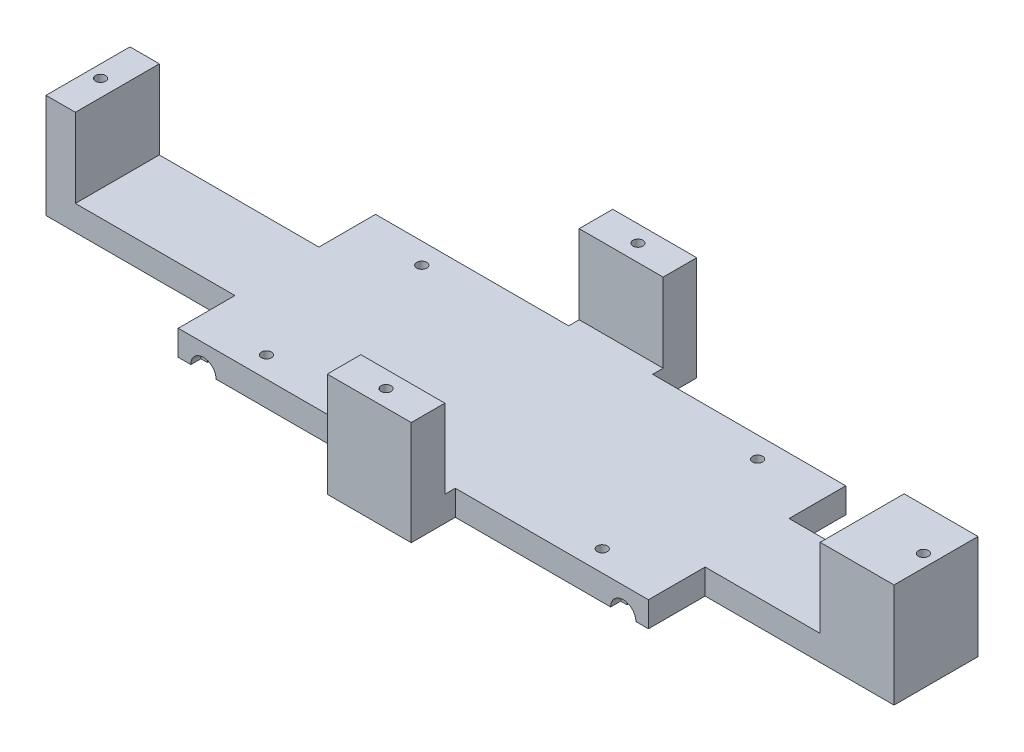
SolidWorks part; units mm, degrees
ref_plane "前视基准面" through (0, 0, 0) normal (0, 0, 1) x (1, 0, 0)
ref_plane "上视基准面" through (0, 0, 0) normal (0, 1, 0) x (1, 0, 0)
ref_plane "右视基准面" through (0, 0, 0) normal (1, 0, 0) x (0, 0, -1)
other "Configuration Table"
sketch "草图1" plane through (0, 0, 0) normal (0, 1, 0) x (1, 0, 0)
  line L0 (-20, 9.25) -> (20, 9.25) construction
  line L1 (-28, -11.75) -> (28, -11.75)
  line L2 (-28, -11.75) -> (-28, 11.75)
  line L3 (-28, 11.75) -> (28, 11.75)
  line L4 (28, -11.75) -> (28, 11.75)
  line L5 (-28, -11.75) -> (28, 11.75) construction
  line L6 (-28, 11.75) -> (28, -11.75) construction
  line L8 (20, 9.25) -> (20, -9.25) construction
  line L10 (0, 0) -> (0, 9.25) construction
  line L12 (0, 0) -> (20, 0) construction
  circle A1 centre (-20, 9.25) radius 0.6
  circle A2 centre (-20, -9.25) radius 0.6
  circle A3 centre (20, 9.25) radius 0.6
  circle A4 centre (20, -9.25) radius 0.6
  point P0 (0, 0)
  dimension "D3" = 40
  dimension "D4" = 18.5
  dimension "D1" = 56
  dimension "D2" = 23.5
  dimension "D7" = 1.2
extrude "凸台-拉伸1" add sketch "草图1" along normal blind 3
sketch "草图2" plane through (0, 0, 11.75) normal (0, 0, 1) x (1, 0, 0)
  line L0 (-28, 0) -> (28, 0) construction
  line L1 (-25, 0) -> (25, 0) construction
  circle A0 centre (-25, 0) radius 0.75
  circle A1 centre (-25, 0) radius 1.5
  circle A2 centre (25, 0) radius 0.75
  circle A3 centre (25, 0) radius 1.5
  dimension "D1" = 1.5
  dimension "D2" = 3
  dimension "D3" = 50
extrude "切除-拉伸1" cut sketch "草图2" against normal through all contours A0 | A2
extrude "切除-拉伸2" cut sketch "草图2<3>" against normal blind 1.2
sketch "草图2<3>" plane through (0, 0, 11.75) normal (0, 0, 1) x (1, 0, 0) same geometry as "草图2"
extrude "切除-拉伸3" cut sketch "草图2<4>" along normal blind 1.2 from surface starting at face at (0, 0.9375, -11.75)
sketch "草图2<4>" plane through (0, 0, 11.75) normal (0, 0, 1) x (1, 0, 0) same geometry as "草图2"
sketch "草图3" plane through (0, 0, 0) normal (0, -1, 0) x (1, 0, 0)
  line L0 (-28, -11.75) -> (-28, 11.75) construction
  line L1 (-28, -5) -> (-50.5, -5)
  line L2 (-28, -5) -> (-28, 5)
  line L3 (-28, 5) -> (-50.5, 5)
  line L4 (-50.5, -5) -> (-50.5, 5)
  line L5 (28, 11.75) -> (28, -11.75) construction
  line L6 (28, 5) -> (50.5, 5)
  line L7 (28, 5) -> (28, -5)
  line L8 (28, -5) -> (50.5, -5)
  line L9 (50.5, 5) -> (50.5, -5)
  line L10 (-50.5, 0) -> (0, 0) construction
  line L11 (-5, -17) -> (5, -17)
  line L12 (-5, -17) -> (-5, 17)
  line L13 (-5, 17) -> (5, 17)
  line L14 (5, -17) -> (5, 17)
  line L15 (0, 0) -> (50.5, 0) construction
  line L16 (0, -17) -> (0, 0) construction
  line L17 (0, 0) -> (0, 17) construction
  dimension "D1" = 17
  dimension "D2" = 10
  dimension "D3" = 22.5
  dimension "D4" = 10
extrude "凸台-拉伸2" add sketch "草图3" against normal blind 12.4
sketch "草图4" plane through (0, 12.4, 0) normal (0, 1, 0) x (1, 0, 0)
  line L0 (0, 15) -> (0, -15) construction
  line L1 (49, 0) -> (-49, 0) construction
  circle A0 centre (0, 15) radius 0.6
  circle A1 centre (0, -15) radius 0.6
  circle A2 centre (49, 0) radius 0.6
  circle A3 centre (-49, 0) radius 0.6
  dimension "D1" = 1.2
  dimension "D2" = 30
  dimension "D3" = 98
extrude "切除-拉伸4" cut sketch "草图4" against normal blind 2
sketch "草图5" plane through (0, 12.4, 0) normal (0, 1, 0) x (1, 0, 0)
  line L1 (41.7, 13) -> (-42.8, 13)
  line L2 (41.7, 13) -> (41.7, -13)
  line L3 (41.7, -13) -> (-42.8, -13)
  line L4 (-42.8, 13) -> (-42.8, -13)
  line L5 (-47, 8) -> (-42.8, 8)
  line L6 (-47, 8) -> (-47, -7.1)
  line L7 (-47, -7.1) -> (-42.8, -7.1)
  line L8 (-42.8, 8) -> (-42.8, -7.1)
  dimension "D1" = 84.5
  dimension "D2" = 26
  dimension "D3" = 13
  dimension "D4" = 42.8
  dimension "D5" = 4.2
  dimension "D6" = 15.1
  dimension "D7" = 8
extrude "切除-拉伸5" cut sketch "草图5" against normal up to surface (9.4 mm away) contours L5 L8 L7 L6 | L1 L4 L3 L2 up to face at (-20, 3, 9.85)
